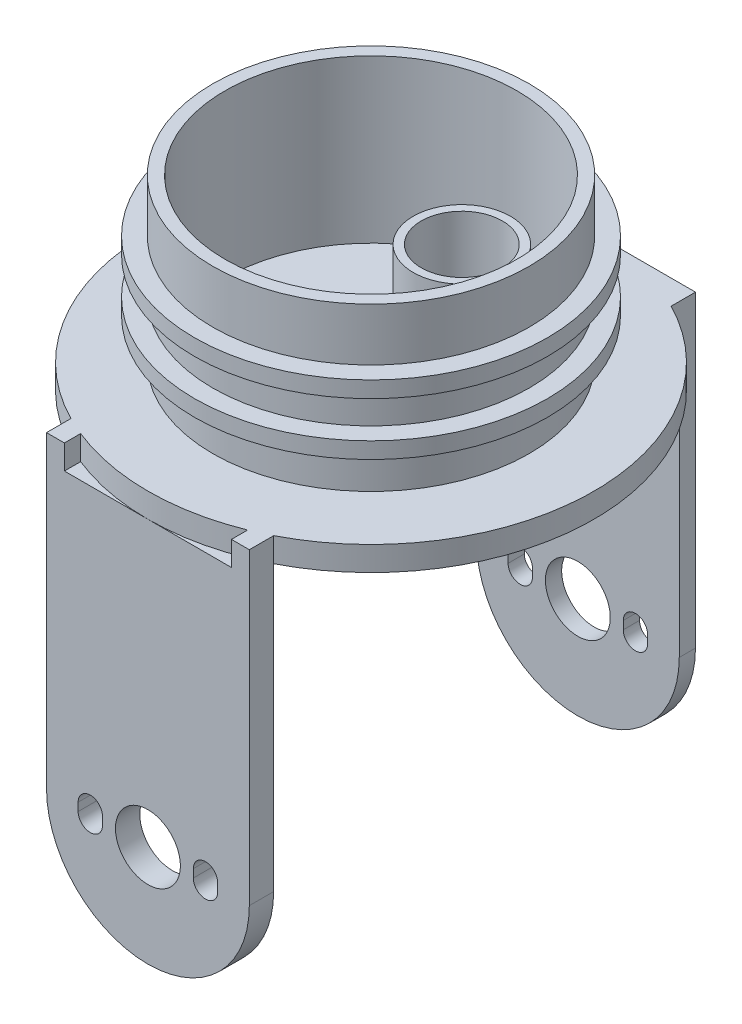
SolidWorks part; units mm, degrees
ref_plane "前基準面" through (0, 0, 0) normal (0, 0, 1) x (1, 0, 0)
ref_plane "上基準面" through (0, 0, 0) normal (0, 1, 0) x (1, 0, 0)
ref_plane "右基準面" through (0, 0, 0) normal (1, 0, 0) x (0, 0, -1)
sketch "草圖1" plane through (0, 0, 0) normal (0, 1, 0) x (1, 0, 0)
  circle A0 centre (0, 0) radius 19.5
  circle A1 centre (0, 0) radius 18
  dimension "D1" = 39
  dimension "D2" = 36
extrude "填料-伸長1" add sketch "草圖1" along normal blind 20
sketch "草圖3" plane through (0, 0, 0) normal (0, -1, 0) x (1, 0, 0)
  circle A0 centre (0, 0) radius 27.5
  dimension "D1" = 55
extrude "填料-伸長2" add sketch "草圖3" along normal blind 3
sketch "草圖4" plane through (0, 0, 0) normal (0, 0, 1) x (1, 0, 0)
  line L0 (0, 20) -> (0, -52.6673) construction
  line L1 (18, 20) -> (-18, 20) construction
  line L2 (-27.5, -3) -> (27.5, -3) construction
  line L3 (-10, -3) -> (10, -3)
  line L4 (-10, -3) -> (-10, -63)
  line L5 (-10, -63) -> (10, -63)
  line L6 (10, -3) -> (10, -63)
  line L8 (-6.5, -28) -> (6.5, -28)
  line L9 (-6.5, -28) -> (-6.5, -53)
  line L10 (-6.5, -53) -> (6.5, -53)
  line L11 (6.5, -28) -> (6.5, -53)
  dimension "D1" = 10
  dimension "D2" = 10
  dimension "D3" = 60
  dimension "D4" = 6.5
  dimension "D5" = 6.5
  dimension "D6" = 25
  dimension "D7" = 25
ref_plane "平面2" through (0, -3, 0) normal (0, -1, 0) x (-1, 0, 0)
sketch "草圖10" plane through (0, -3, 0) normal (0, -1, 0) x (-1, 0, 0)
  circle A0 centre (0, 11.196) radius 5
  circle A1 centre (0, 11.196) radius 6
  dimension "D1" = 10
  dimension "D2" = 12
extrude "填料-伸長6" add sketch "草圖10" against normal blind 10
sketch "草圖11" plane through (0, -3, 0) normal (0, -1, 0) x (-1, 0, 0)
  circle A0 centre (0, 11.196) radius 5.0075
extrude "除料-伸長4" cut sketch "草圖11" along normal blind 19 and the other way blind 10
ref_plane "平面4" through (0, 0, -3) normal (0, 0, 1) x (1, 0, 0)
ref_plane "平面5" through (0, 0, 0) normal (0, 1, 0) x (1, 0, 0)
ref_plane "平面6" through (0, 7, 0) normal (0, -1, 0) x (-1, 0, 0)
sketch "草圖25" plane through (0, 7, 0) normal (0, -1, 0) x (-1, 0, 0)
  circle A0 centre (0, 0) radius 21.75
  circle A1 centre (0, 0) radius 19.5
  dimension "D1" = 43.5
extrude "填料-伸長12" add sketch "草圖25" along normal blind 2
ref_plane "平面10" through (0, 10.5, 0) normal (0, -1, 0) x (-1, 0, 0)
sketch "草圖26" plane through (0, 10.5, 0) normal (0, -1, 0) x (-1, 0, 0)
  circle A0 centre (0, 0) radius 21.75
  circle A1 centre (0, 0) radius 19.5
extrude "填料-伸長13" add sketch "草圖26" against normal blind 2 from offset 1 offset against normal yes
sketch "草圖27" plane through (0, -3, 0) normal (0, -1, 0) x (1, 0, 0)
  line L0 (0, 0) -> (-12.5, 0)
  line L1 (46.0389, 0) -> (-46.0389, 0) construction
  line L2 (-12.5, 0) -> (-12.5, 25.5)
  line L3 (-12.5, 25.5) -> (12.5, 25.5)
  line L4 (12.5, 25.5) -> (12.5, 0)
  line L5 (12.5, 0) -> (-12.5, 0)
  line L6 (-12.5, 0) -> (-12.5, -25.5)
  line L7 (-12.5, -25.5) -> (12.5, -25.5)
  line L8 (12.5, -25.5) -> (12.5, 0)
  circle M5 centre (0, -11.196) radius 5.0075
  circle M6 centre (0, 0) radius 27.5
extrude "填料-伸長14" add sketch "草圖27" against normal blind 3 contours L8 L5 L0 L6 L7 M6 M5 | L5 L4 L3 L2 L0 M6 | L6 L7 M6 | L7 L8 M6 | L4 L3 M6 | L3 L2 M6 region at (6.25, -3, -0.3571) region at (0, -3, 12.7084) region at (-11.7799, -3, 25.1714) region at (-11.7799, -3, -25.1714) region at (11.7799, -3, 25.1714) region at (11.7799, -3, -25.1714)
sketch "草圖28" plane through (0, 0, -25.5) normal (0, 0, -1) x (-1, 0, 0)
  line L0 (12.5, -3) -> (12.5, -38)
  line L1 (12.5, -38) -> (-12.5, -38)
  line L2 (-12.5, -38) -> (-12.5, 0)
  line L3 (-12.5, 0) -> (12.5, 0)
  line L4 (12.5, 0) -> (12.5, -3) construction
  line L5 (12.5, 0) -> (12.5, -3)
  line L6 (-7.1, -37.5) -> (-7.1, -38.5) construction
  line L7 (-5.6, -37.5) -> (-5.6, -38.5)
  line L8 (-8.6, -37.5) -> (-8.6, -38.5)
  line L9 (12.5, -3) -> (-12.5, -3)
  line L10 (7.1, -37.5) -> (7.1, -38.5) construction
  line L11 (8.6, -37.5) -> (8.6, -38.5)
  line L12 (5.6, -37.5) -> (5.6, -38.5)
  arc A0 (12.5, -38) -> (-12.5, -38) centre (0, -38) cw
  circle A1 centre (0, -38) radius 4
  arc A2 (-5.6, -37.5) -> (-8.6, -37.5) centre (-7.1, -37.5) ccw
  arc A3 (-8.6, -38.5) -> (-5.6, -38.5) centre (-7.1, -38.5) ccw
  arc A4 (8.6, -37.5) -> (5.6, -37.5) centre (7.1, -37.5) ccw
  arc A5 (5.6, -38.5) -> (8.6, -38.5) centre (7.1, -38.5) ccw
  point P14 (-7.1, -38)
  point P19 (-7.1, -36)
  point P20 (-7.1, -40)
  point P26 (7.1, -38)
  point P31 (7.1, -36)
  point P32 (7.1, -40)
  line M17 (10.2956, 0) -> (10.2956, -3)
  line M18 (10.2956, -3) -> (12.5, -3)
  line M19 (12.5, -3) -> (12.5, 0)
  line M20 (12.5, 0) -> (10.2956, 0)
  dimension "D1" = 8
  dimension "D2" = 4
  dimension "D3" = 3
  dimension "D4" = 5.6
  dimension "D5" = 4
  dimension "D6" = 3
  dimension "D7" = 5.6
  dimension "D8" = 35
extrude "填料-伸長17" add sketch "草圖28" along normal blind 2 contours A4 L11 L1 L0 L9 L2 L8 A2 L7 A1 L12 M18 | L9 L3 L2 M17 | M20 M17 M18 M19 | A5 L12 L1 A1 L7 A3 L8 A0 L11 region at (-11.3978, -1.5, -25.5) region at (0, -19.8277, -25.5) region at (0, -43.9487, -25.5) region at (1.1022, -1.5, -25.5)
extrude "填料-伸長19" add sketch "草圖28<15>" against normal blind 53 contours A4 L11 L1 L0 L9 L2 L8 A2 L7 A1 L12 M18 | A5 L12 L1 A1 L7 A3 L8 A0 L11 region at (0, -19.8277, -25.5) region at (0, -43.9487, -25.5)
sketch "草圖28<15>" plane through (0, 0, -25.5) normal (0, 0, -1) x (-1, 0, 0) same geometry as "草圖28"
sketch "草圖32" plane through (0, 0, 25.5) normal (0, 0, 1) x (1, 0, 0)
  line L0 (10.2956, -3) -> (12.5, -3)
  line L1 (-30.25, -3) -> (30.25, -3) construction
  line L2 (12.5, -3) -> (0, -3) construction
  line L3 (12.5, -3) -> (12.5, 0)
  line L4 (19.5, 0) -> (-19.5, 0) construction
  line L5 (12.5, 0) -> (12.5, -3) construction
  line L6 (12.5, 0) -> (10.2956, 0)
  line L7 (10.2956, 0) -> (10.2956, -3) construction
  line L8 (10.2956, 0) -> (10.2956, -3)
  line L9 (-10.2956, 0) -> (-10.2956, -3)
  line L10 (-10.2956, -3) -> (-10.2956, 0) construction
  line L11 (0, -3) -> (-12.5, -3) construction
  line L12 (-12.5, -3) -> (-10.2956, -3) construction
  line L13 (-10.2956, -3) -> (-12.5, -3)
  line L14 (-12.5, -3) -> (-12.5, 0)
  line L15 (-12.5, -3) -> (-12.5, 0) construction
  line L16 (-12.5, 0) -> (-10.2956, 0)
extrude "填料-伸長20" add sketch "草圖32" along normal blind 2
extrude "除料-伸長8" cut sketch "草圖28<18>" against normal blind 50 contours A4 L11 L1 L0 L9 L2 L8 A2 L7 A1 L12 M18 | A5 L12 L1 A1 L7 A3 L8 A0 L11 region at (0, -19.8277, -25.5) region at (0, -43.9487, -25.5)
sketch "草圖28<18>" plane through (0, 0, -25.5) normal (0, 0, -1) x (-1, 0, 0) same geometry as "草圖28"
